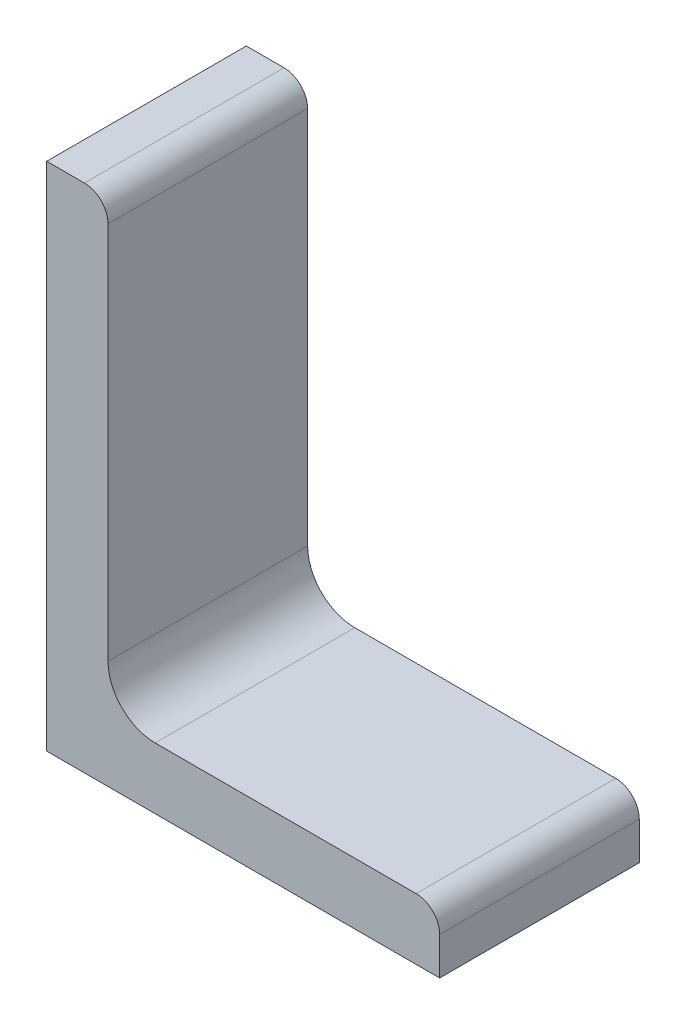
SolidWorks part; units mm, degrees
ref_plane "Front Plane" through (0, 0, 0) normal (0, 0, 1) x (1, 0, 0)
ref_plane "Top Plane" through (0, 0, 0) normal (0, 1, 0) x (1, 0, 0)
ref_plane "Right Plane" through (0, 0, 0) normal (1, 0, 0) x (0, 0, -1)
sketch "Sketch1" plane through (0, 0, 0) normal (0, 0, 1) x (1, 0, 0)
  line L1 (0, 0) -> (50, 0)
  line L2 (0, 0) -> (0, 65)
  line L3 (0, 65) -> (4.8, 65)
  line L4 (50, 0) -> (50, 4.8)
  line L6 (7.8, 62) -> (7.8, 13.8)
  line L7 (13.8, 7.8) -> (47, 7.8)
  arc A0 (7.8, 13.8) -> (13.8, 7.8) centre (13.8, 13.8) ccw
  arc A1 (4.8, 65) -> (7.8, 62) centre (4.8, 62) cw
  arc A2 (50, 4.8) -> (47, 7.8) centre (47, 4.8) ccw
  dimension "Radius_root" = 6
  dimension "Radius_toe" = 3
  dimension "Width" = 50
  dimension "Thickness" = 7.8
  dimension "Depth" = 65
extrude "BaseSection" add sketch "Sketch1" along normal mid plane 25.4
